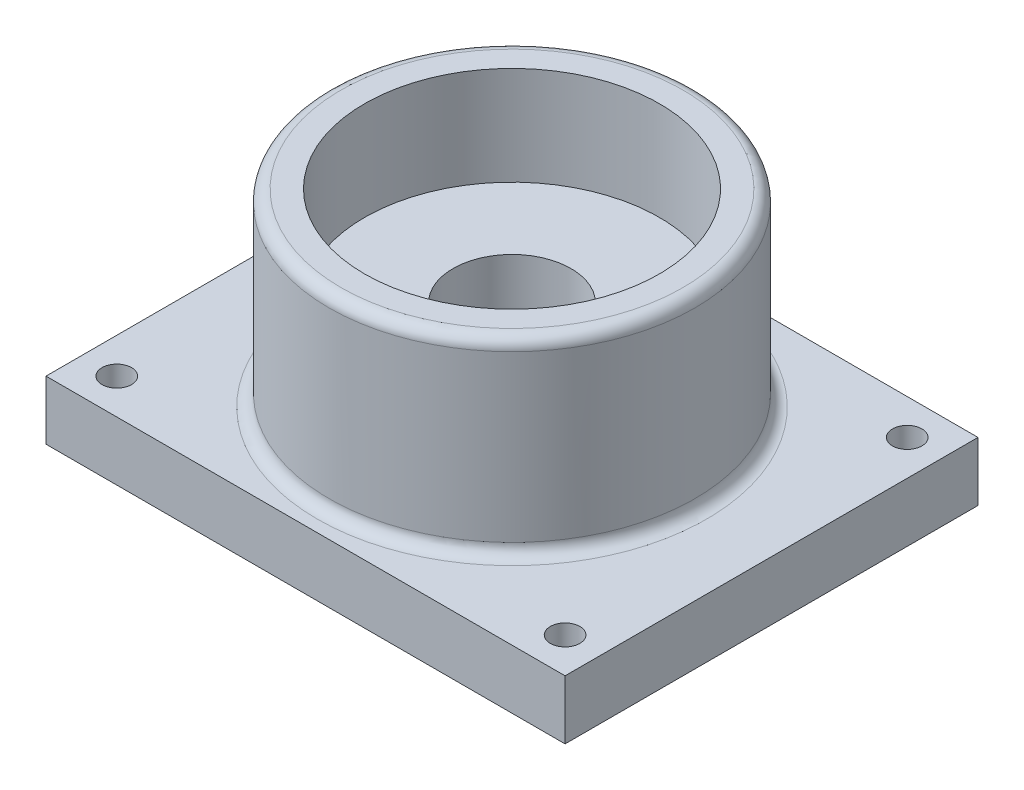
SolidWorks part; units mm, degrees
ref_plane "Front Plane" through (0, 0, 0) normal (0, 0, 1) x (1, 0, 0)
ref_plane "Top Plane" through (0, 0, 0) normal (0, 1, 0) x (1, 0, 0)
ref_plane "Right Plane" through (0, 0, 0) normal (1, 0, 0) x (0, 0, -1)
sketch "Sketch1" plane through (0, 0, 0) normal (0, 1, 0) x (1, 0, 0)
  circle A0 centre (0, 0) radius 15.5
  dimension "D1" = 31
extrude "Boss-Extrude1" add sketch "Sketch1" along normal blind 16
ref_plane "Plane1" through (0, 0, 0) normal (0, -1, 0) x (-1, 0, 0)
sketch "Sketch16" plane through (0, 0, 0) normal (0, -1, 0) x (1, 0, 0)
  line L0 (0, 0) -> (22, 17.5) construction
  line L1 (-22, 17.5) -> (22, 17.5)
  line L2 (-22, 17.5) -> (-22, -17.5)
  line L3 (-22, -17.5) -> (22, -17.5)
  line L4 (22, 17.5) -> (22, -17.5)
  line L5 (-22, 17.5) -> (22, -17.5) construction
  circle A3 centre (-19, 14.5) radius 1.25
  circle A6 centre (19, 14.5) radius 1.25
  circle A7 centre (19, -14.5) radius 1.25
  circle A8 centre (-19, -14.5) radius 1.25
  point P0 (0, 0)
  dimension "D3" = 2
  dimension "D5" = 2.5
  dimension "D8" = 3
  dimension "D1" = 35
  dimension "D2" = 44
  dimension "D4" = 2
  dimension "D9" = 3
extrude "Boss-Extrude6" add sketch "Sketch16" along normal blind 5
sketch "Sketch17" plane through (0, 16, 0) normal (0, 1, 0) x (1, 0, 0)
  circle A0 centre (0, 0) radius 9.75
  dimension "D1" = 19.5
extrude "Cut-Extrude5" cut sketch "Sketch17" against normal blind 6
sketch "Sketch18" plane through (0, 10, 0) normal (0, 1, 0) x (1, 0, 0)
  circle A0 centre (0, 0) radius 5
  dimension "D1" = 10
extrude "Cut-Extrude7" cut sketch "Sketch18" against normal blind 19
fillet "Fillet4" radius 1 1 edges at (0, 0, 15.5)
fillet "Fillet1" radius 1 1 edges at (0, 16, 9.75)
fillet "Fillet3" radius 1 1 edges at (0, 16, 15.5)
sketch "Sketch2" plane through (0, 0, 0) normal (0, -1, 0) x (-1, 0, 0)
  circle A0 centre (0, 0) radius 7
  dimension "D1" = 14
extrude "Boss-Extrude3" [suppressed] add sketch "Sketch2" along normal blind 20 contours A0
ref_plane "Plane3" through (0, 16, 0) normal (0, 1, 0) x (1, 0, 0)
sketch "Sketch5" plane through (0, 16, 0) normal (0, 1, 0) x (1, 0, 0)
  circle A0 centre (0, 0) radius 12.5
  dimension "D1" = 25
extrude "Cut-Extrude1" cut sketch "Sketch5" against normal blind 8.352
ref_plane "Plane4" through (0, 7.648, 0) normal (0, 1, 0) x (1, 0, 0)
sketch "Sketch6" plane through (0, 7.648, 0) normal (0, 1, 0) x (1, 0, 0)
  circle A0 centre (0, 0) radius 5
  dimension "D1" = 10
extrude "Cut-Extrude2" [suppressed] cut sketch "Sketch6" against normal blind 30
ref_plane "Plane10" [suppressed] through (0, -20, 0) normal (0, -1, 0) x (-1, 0, 0)
sketch "Sketch12" [suppressed] plane through (0, -20, 0) normal (0, -1, 0) x (-1, 0, 0)
  line L1 (-22, 17.5) -> (22, 17.5)
  line L2 (-22, 17.5) -> (-22, -17.5)
  line L3 (-22, -17.5) -> (22, -17.5)
  line L4 (22, 17.5) -> (22, -17.5)
  line L5 (-22, 17.5) -> (22, -17.5) construction
  line L6 (-22, -17.5) -> (22, 17.5) construction
  circle A1 centre (-19, -14.5) radius 1.5
  circle A2 centre (19, -14.5) radius 1.5
  circle A3 centre (19, 14.5) radius 1.5
  circle A4 centre (-19, 14.5) radius 1.5
  point P0 (0, 0)
  dimension "D1" = 44
  dimension "D3" = 3
  dimension "D2" = 35
  dimension "D4" = 3
  dimension "D5" = 2
  dimension "D6" = 2
extrude "Boss-Extrude4" [suppressed] add sketch "Sketch12" along normal blind 3 contours L2 L3 L4 L1
sketch "Sketch14" [suppressed] plane through (0, -20, 0) normal (0, -1, 0) x (-1, 0, 0)
  line L0 (-22, -17.5) -> (22, -17.5) construction
  line L1 (-22, 17.5) -> (-22, -17.5) construction
  circle A0 centre (-19, -14.5) radius 1.5
  circle A1 centre (19, -14.5) radius 1.5
  circle A2 centre (19, 14.5) radius 1.5
  circle A3 centre (-19, 14.5) radius 1.5
  dimension "D1" = 3
  dimension "D3" = 3
  dimension "D2" = 3
  dimension "D4" = 2
  dimension "D5" = 2
extrude "Cut-Extrude3" [suppressed] cut sketch "Sketch14" along normal blind 3
sketch "Sketch15" [suppressed] plane through (0, -20, 0) normal (0, -1, 0) x (-1, 0, 0)
  circle A0 centre (0, 0) radius 5
  dimension "D1" = 10
extrude "Cut-Extrude4" [suppressed] cut sketch "Sketch15" along normal blind 3
